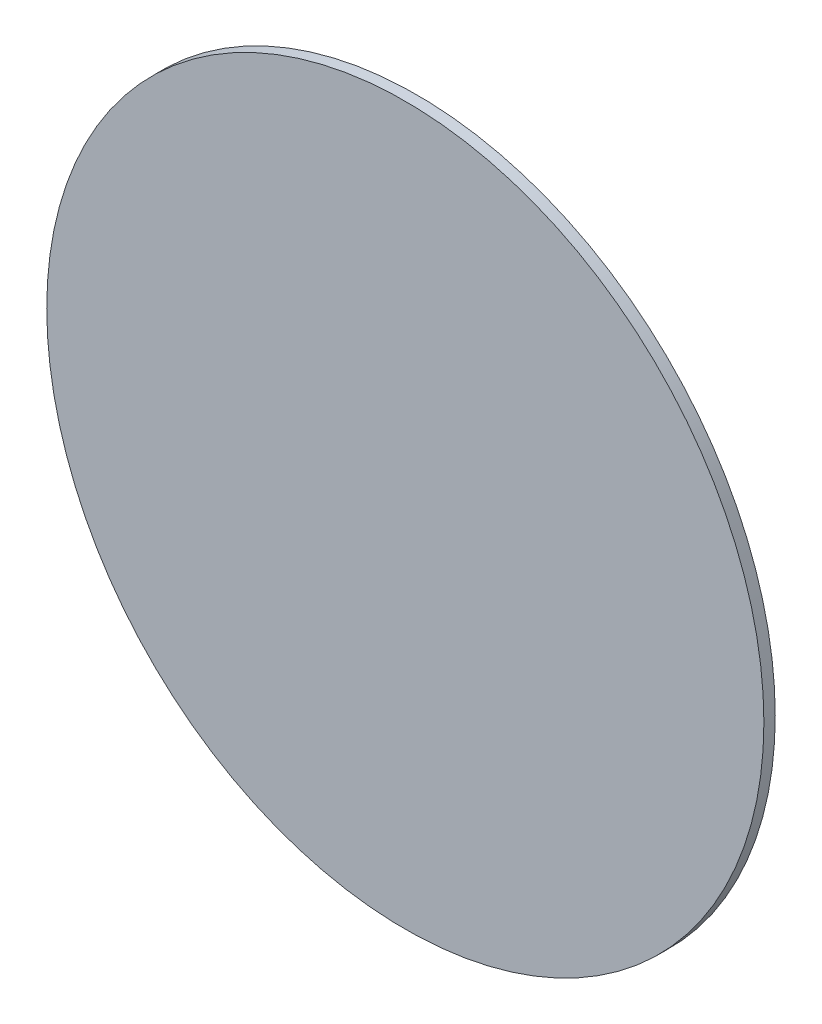
SolidWorks part; units mm, degrees
material "AISI 304"
ref_plane "Front Plane" through (0, 0, 0) normal (0, 0, 1) x (1, 0, 0)
ref_plane "Top Plane" through (0, 0, 0) normal (0, 1, 0) x (1, 0, 0)
ref_plane "Right Plane" through (0, 0, 0) normal (1, 0, 0) x (0, 0, -1)
sketch "End_Lid_Profile" plane through (0, 0, 0) normal (0, 0, 1) x (1, 0, 0)
  circle A0 centre (0, 0) radius 158
  dimension "D1" = 316
extrude "End_Lid_Disc_5mm" add sketch "End_Lid_Profile" along normal blind 5
ref_axis "Lid_Axis" through (0, 0, -0.25) along (0, 0, 1)
ref_plane "Lid_Outer_Plane" through (0, 0, 5) normal (0, 0, 1) x (1, 0, 0)
